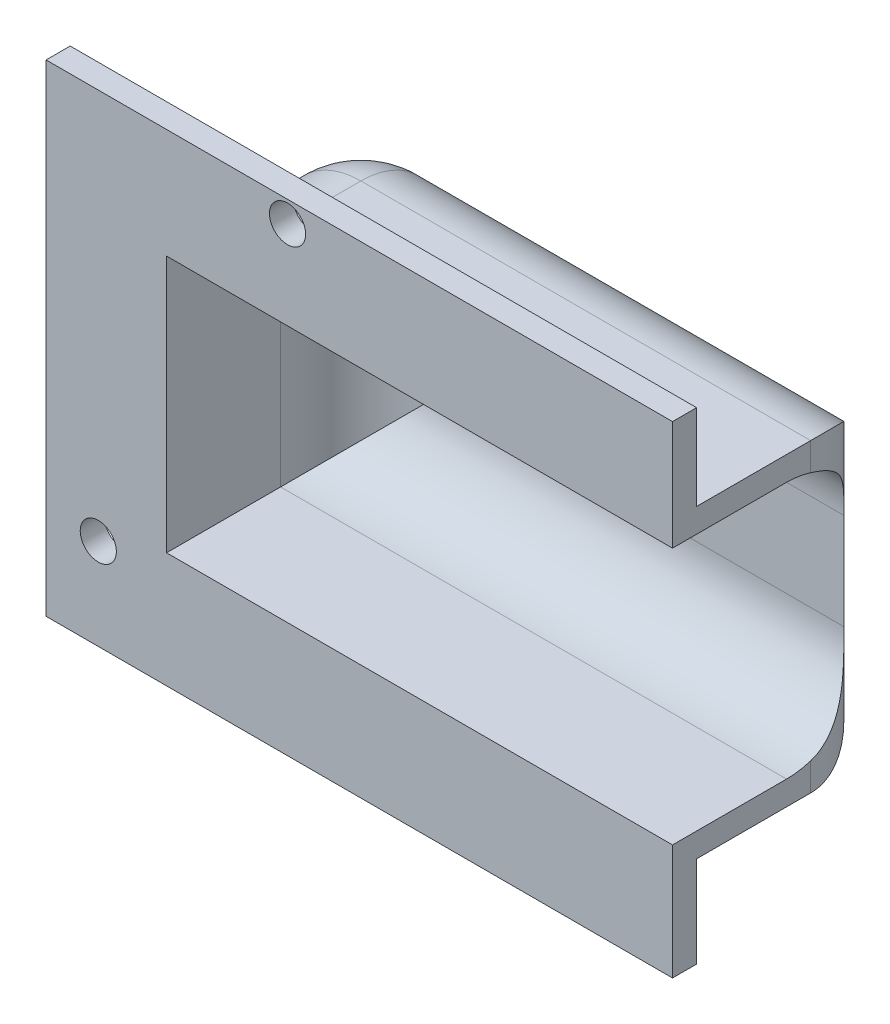
SolidWorks part; units mm, degrees
ref_plane "Front Plane" through (0, 0, 0) normal (1, 0, 0) x (0, 1, 0)
ref_plane "Top Plane" through (0, 0, 0) normal (0, 0, 1) x (0, 1, 0)
ref_plane "Right Plane" through (0, 0, 0) normal (0, 1, 0) x (-1, 0, 0)
sketch "Sketch1" plane through (0, 0, 0) normal (0, 0, 1) x (0, 1, 0)
  line L1 (-16, -30) -> (16, -30)
  line L2 (-16, -30) -> (-16, 30)
  line L3 (-16, 30) -> (16, 30)
  line L4 (16, -30) -> (16, 30)
  line L5 (-16, -30) -> (16, 30) construction
  line L6 (-16, 30) -> (16, -30) construction
  point P0 (0, 0)
  point P5 (0, 0)
  dimension "D1" = 60
  dimension "D2" = 32
extrude "Boss-Extrude1" add sketch "Sketch1" along normal blind 24.2
shell "Shell1" thickness 3 removed face at (0, 0, 24.2) outward yes
sketch "Sketch3" plane through (0, 0, 24.2) normal (0, 0, 1) x (1, 0, 0)
  line L0 (33, -19) -> (33, 19) construction
  line L1 (30, 16) -> (33, 16)
  line L2 (30, 16) -> (30, -16)
  line L3 (30, -16) -> (33, -16)
  line L4 (33, 16) -> (33, -16)
  line L5 (30, 16) -> (33, -16) construction
  line L6 (30, -16) -> (33, 16) construction
  point P4 (31.5, 0)
extrude "Cut-Extrude1" cut sketch "Sketch3" against normal blind 24.2
sketch "Sketch4" plane through (0, 0, 0) normal (0, 0, 1) x (0, 1, 0)
  line L5 (-30.3511, -33) -> (29.6489, -33)
  line L6 (-30.3511, -33) -> (-30.3511, 45)
  line L7 (-30.3511, 45) -> (29.6489, 45)
  line L8 (29.6489, -33) -> (29.6489, 45)
  line L9 (-30.3511, -33) -> (29.6489, 45) construction
  line L10 (-30.3511, 45) -> (29.6489, -33) construction
  point P4 (-0.3511, 6)
  dimension "D1" = 78
  dimension "D2" = 60
extrude "Boss-Extrude2" add sketch "Sketch4" against normal blind 3 from surface starting at face at (0.75, 0, 24.2)
sketch "Sketch5" plane through (0, 0, 24.2) normal (0, 0, 1) x (1, 0, 0)
  line L1 (-30, -16) -> (30, -16)
  line L2 (-30, -16) -> (-30, 16)
  line L3 (-30, 16) -> (30, 16)
  line L5 (-30, -16) -> (30, 16) construction
  line L6 (-30, 16) -> (30, -16) construction
  line L11 (33, 31.7291) -> (43.5837, 31.7291)
  line L13 (43.5837, -32.3435) -> (33, -32.3435)
  line L15 (43.5837, 31.7291) -> (43.5837, -32.3435)
  line L16 (33, 16) -> (33, 31.7291)
  line L17 (33, -30.3511) -> (33, 29.6489) construction
  line L18 (30, 16) -> (33, 16)
  line L19 (30, -16) -> (33, -16)
  line L20 (33, -16) -> (33, -32.3435)
extrude "Cut-Extrude2" cut sketch "Sketch5" against normal blind 3
sketch "Sketch6" plane through (0, 0, 21.2) normal (0, 0, -1) x (1, 0, 0)
  line L0 (30, 19) -> (-36.25, 19) construction
  line L2 (-14.9361, -19) -> (-14.9361, -27) construction
  line L4 (33, -19) -> (-33, -19) construction
  circle A0 centre (-14.9361, -27) radius 2.25
  circle A1 centre (-38.5, 19) radius 2.25
  point P10 (0, 0)
  dimension "D2" = 4.5
  dimension "D1" = 66.25
  dimension "D3" = 8
extrude "Cut-Extrude3" cut sketch "Sketch6" against normal blind 3 contours A0 | A1 region at (-14.9361, 27, 21.2)
fillet "Fillet2" radius 10 4 edges at (-33, 0, -3) (0, -19, -3) (33, 0, -3) (0, 19, -3)
fillet "Fillet3" radius 10 3 edges at (0.0707, 16, 0) (-30, 0, 0) (0.0707, -16, 0)
fillet "Fillet4" radius 10 4 edges at (-30.0711, 16.0711, -0.0711) (-30.0711, -16.0711, -0.0711) (-33, 19, 14.1) (-33, -19, 14.1)
